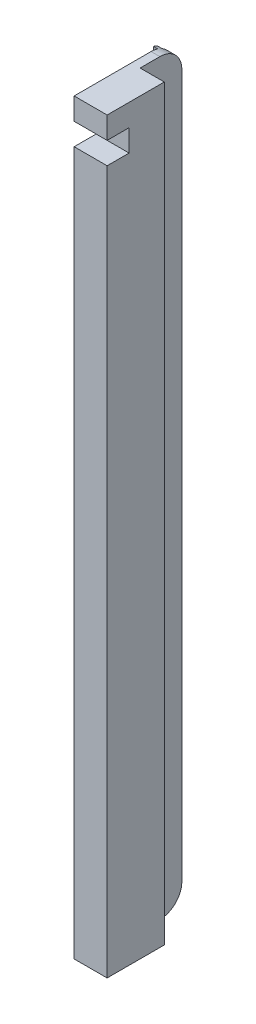
SolidWorks part; units mm, degrees
ref_plane "정면" through (0, 0, 0) normal (0, 0, 1) x (1, 0, 0)
ref_plane "윗면" through (0, 0, 0) normal (0, 1, 0) x (1, 0, 0)
ref_plane "우측면" through (0, 0, 0) normal (1, 0, 0) x (0, 0, -1)
sketch "스케치1" plane through (0, 0, 0) normal (0, 0, 1) x (1, 0, 0)
  line L0 (-318.5049, 0) -> (318.5049, 0) construction
  line L1 (0, 0) -> (0, -258.8265) construction
  line L2 (-168, 0) -> (168, 0)
  line L3 (-168, -20) -> (168, -20)
  line L4 (168, -20) -> (168, 0) construction
  line L5 (168, -20) -> (168, -340)
  line L6 (172, -340) -> (172, 0)
  line L7 (168, 0) -> (183, 0)
  line L8 (183, 0) -> (183, -340)
  line L9 (183, -340) -> (168, -340)
  line L10 (-168, -20) -> (-168, 0) construction
  line L11 (-183, -340) -> (-168, -340)
  line L12 (-183, 0) -> (-183, -340)
  line L13 (-168, 0) -> (-183, 0)
  line L14 (-172, -340) -> (-172, 0)
  line L15 (-168, -20) -> (-168, -340)
  line L16 (168, -20) -> (168, 0)
  line L17 (-168, -20) -> (-168, 0)
  point P14 (0, -20)
  dimension "D1" = 168
  dimension "D2" = 20
  dimension "D3" = 4
  dimension "D4" = 340
  dimension "D5" = 15
extrude "보스-돌출1" add sketch "스케치1" along normal blind 26 contours L3 L5 L9 L8 L7 L2 L13 L12 L11 L15
extrude "보스-돌출2" add sketch "스케치1<4>" against normal blind 19 contours L16 L5 L9 L6 L7 | L15 L17 L13 L14 L11 region at (-170, -170, 0) region at (170, -170, 0)
sketch "스케치1<4>" plane through (0, 0, 0) normal (0, 0, 1) x (1, 0, 0) same geometry as "스케치1"
fillet "필렛1" radius 10 4 edges at (-170, 0, -19) (170, 0, -19) (170, -340, -19) (-170, -340, -19)
sketch "스케치2" plane through (172, 0, 0) normal (1, 0, 0) x (0, 0, -1)
  line L0 (14, -340) -> (14, 0)
  line L1 (12, 0) -> (12, -340)
  line L4 (19, -330) -> (19, -10)
  line L5 (9, 0) -> (0, 0)
  line L6 (0, 0) -> (0, -340)
  line L7 (0, -340) -> (9, -340)
  line L8 (19, -330) -> (19, -10)
  line L9 (9, 0) -> (0, 0)
  line L10 (0, 0) -> (0, -340)
  line L11 (0, -340) -> (9, -340)
  arc A2 (19, -10) -> (9, 0) centre (9, -10) ccw
  arc A3 (9, -340) -> (19, -330) centre (9, -330) ccw
  arc A4 (19, -10) -> (9, 0) centre (9, -10) ccw
  arc A5 (9, -340) -> (19, -330) centre (9, -330) ccw
  dimension "D2" = 5
  dimension "D3" = 2
  dimension "D1" = 0
sketch "스케치3" plane through (168, 0, 0) normal (-1, 0, 0) x (0, 0, 1)
  line L0 (-12, 0) -> (-12, -340) construction
  line L1 (-14, -340) -> (-14, 0) construction
  line L2 (-12, 0) -> (-12, -340)
  line L3 (-14, -340) -> (-14, 0)
  line L4 (-19, -10) -> (-19, -330)
  line L5 (0, 0) -> (-9, 0)
  line L6 (0, -340) -> (0, 0)
  line L7 (-9, -340) -> (0, -340)
  line L8 (-19, -10) -> (-19, -330)
  line L9 (0, 0) -> (-9, 0)
  line L10 (0, -340) -> (0, 0)
  line L11 (-9, -340) -> (0, -340)
  arc A2 (-9, 0) -> (-19, -10) centre (-9, -10) ccw
  arc A3 (-19, -330) -> (-9, -340) centre (-9, -330) ccw
  arc A4 (-9, 0) -> (-19, -10) centre (-9, -10) ccw
  arc A5 (-19, -330) -> (-9, -340) centre (-9, -330) ccw
  arc M8 (-9, 0) -> (-19, -10) centre (-9, -10) ccw
  arc M10 (-19, -330) -> (-9, -340) centre (-9, -330) ccw
  dimension "D1" = 0
extrude "보스-돌출3" add sketch "스케치3" along normal blind 2 contours L3 L2 M10 M8 region at (168, -170, -12.9991)
mirror "대칭 복사1" about plane through (0, 0, 0) normal (1, 0, 0) of "보스-돌출3"
sketch "스케치5" plane through (0, 0, 0) normal (0, 1, 0) x (1, 0, 0)
  line L0 (-7, 0) -> (-7, -26)
  line L1 (7, 0) -> (7, -26)
  line L2 (-168, 0) -> (-168, -6)
  line L3 (-168, -6) -> (-7, -6)
  line L4 (7, -6) -> (168, -6)
  line L5 (168, -6) -> (168, 0)
  line L12 (-168, 0) -> (-168, 9)
  line L13 (-168, 9) -> (-172, 9)
  line L14 (-172, 9) -> (-172, 0)
  line L15 (-172, 0) -> (-183, 0)
  line L16 (-183, 0) -> (-183, -26)
  line L17 (-183, -26) -> (183, -26)
  line L18 (183, -26) -> (183, 0)
  line L19 (183, 0) -> (172, 0)
  line L20 (172, 0) -> (172, 9)
  line L21 (172, 9) -> (168, 9)
  line L22 (168, 9) -> (168, 0)
  line L23 (168, 0) -> (-168, 0)
  line L24 (-168, 0) -> (-168, 9)
  line L25 (-168, 9) -> (-172, 9)
  line L26 (-172, 9) -> (-172, 0)
  line L27 (-172, 0) -> (-183, 0)
  line L28 (-183, 0) -> (-183, -26)
  line L29 (-183, -26) -> (183, -26)
  line L30 (183, -26) -> (183, 0)
  line L31 (183, 0) -> (172, 0)
  line L32 (172, 0) -> (172, 9)
  line L33 (172, 9) -> (168, 9)
  line L34 (168, 9) -> (168, 0)
  line L35 (168, 0) -> (-168, 0)
  line M27 (168, 0) -> (-168, 0)
  dimension "D2" = 7
  dimension "D3" = 7
  dimension "D4" = 6
  dimension "D1" = 0
extrude "컷-돌출1" cut sketch "스케치5" against normal blind 52 contours L2 L3 L0 M27 | L4 L5 L1 M27 region at (-87.5, 0, 3) region at (87.5, 0, 3)
sketch "스케치6" plane through (168, 0, 0) normal (-1, 0, 0) x (0, 0, 1)
  line L0 (26, -20) -> (26, -340) construction
  line L1 (-71.7494, 105.886) -> (84.6976, 105.886)
  line L2 (-71.7494, 105.886) -> (-71.7494, -374.2228)
  line L3 (-71.7494, -374.2228) -> (84.6976, -374.2228)
  line L4 (84.6976, 105.886) -> (84.6976, -374.2228)
  line L5 (-71.7494, 105.886) -> (84.6976, -374.2228) construction
  line L6 (-71.7494, -374.2228) -> (84.6976, 105.886) construction
  line L7 (26, -340) -> (0, -340) construction
  line L8 (26, 0) -> (6, 0)
  line L9 (-9, 0) -> (6, 0)
  line L10 (-9, 0) -> (6, 0)
  line L11 (26, 0) -> (6, 0)
  line L12 (26, -20) -> (26, -340)
  line L13 (26, -20) -> (26, 0)
  line L14 (26, -20) -> (26, 0)
  line L15 (26, -20) -> (26, -340)
  line L16 (26, -20) -> (6, -20)
  line L17 (26, -20) -> (6, -20)
  line L18 (6, -20) -> (6, 0)
  line L19 (6, -20) -> (6, 0)
  point P0 (6.4741, -134.1684)
  line M5 (26, -20) -> (6, -20)
  line M6 (6, -20) -> (6, 0)
  line M7 (6, 0) -> (-9, 0)
  arc M8 (-9, 0) -> (-12, -0.4606) centre (-9, -10) ccw
  line M9 (-12, -0.4606) -> (-12, -339.5394)
  arc M10 (-12, -339.5394) -> (-9, -340) centre (-9, -330) ccw
  line M11 (-9, -340) -> (26, -340)
  line M12 (26, -340) -> (26, -20)
  dimension "D1" = 19.5259
  dimension "D2" = 240.0544
  dimension "D3" = 156.447
  dimension "D4" = 205.8316
extrude "컷-돌출3" cut sketch "스케치6" along normal blind 401 contours L4 L1 L2 L3 L14 L11 M12 M11 M10 M9 M8 M7 | L14 L11 M5 M6 | M12 M5 M6 M7 M8 M9 M10 M11 region at (168, 100.8364, 6.4741) region at (168, -10, 16) region at (168, -175.1122, 6.7138)
sketch "스케치7" plane through (168, 0, 0) normal (-1, 0, 0) x (0, 0, 1)
  line L0 (26, -20) -> (26, -340) construction
  line L1 (26, 0) -> (6, 0) construction
  line L2 (26, -20) -> (26, 0) construction
  line L3 (26, -20) -> (6, -20) construction
  line L4 (26, -340) -> (26, 0)
  line L5 (26, 0) -> (-9, 0)
  line L6 (-19, -10) -> (-19, -330)
  line L7 (-9, -340) -> (26, -340)
  line L8 (26, -340) -> (26, 0)
  line L9 (26, 0) -> (-9, 0)
  line L10 (-19, -10) -> (-19, -330)
  line L11 (-9, -340) -> (26, -340)
  line L12 (6, -20) -> (6, 0) construction
  line L13 (-9, 0) -> (6, 0) construction
  line L14 (-71.7494, 105.886) -> (84.6976, 105.886) construction
  line L15 (84.6976, 105.886) -> (84.6976, -374.2228) construction
  line L16 (-71.7494, -374.2228) -> (84.6976, -374.2228) construction
  line L17 (-71.7494, 105.886) -> (-71.7494, -374.2228) construction
  line L18 (26, -20) -> (26, -340)
  line L19 (26, 0) -> (6, 0)
  line L20 (26, -20) -> (26, 0)
  line L21 (26, -20) -> (6, -20)
  line L22 (6, -20) -> (6, 0)
  line L23 (-9, 0) -> (6, 0)
  line L24 (-71.7494, 105.886) -> (84.6976, 105.886)
  line L25 (84.6976, 105.886) -> (84.6976, -374.2228)
  line L26 (-71.7494, -374.2228) -> (84.6976, -374.2228)
  line L27 (-71.7494, 105.886) -> (-71.7494, -374.2228)
  line L29 (16, -10) -> (26, -10)
  line L30 (16, -10) -> (16, -20)
  line L31 (16, -20) -> (26, -20)
  line L32 (26, -10) -> (26, -20)
  line L33 (16, -10) -> (26, -20) construction
  line L34 (16, -20) -> (26, -10) construction
  arc A2 (-9, 0) -> (-19, -10) centre (-9, -10) ccw
  arc A3 (-19, -330) -> (-9, -340) centre (-9, -330) ccw
  arc A4 (-9, 0) -> (-19, -10) centre (-9, -10) ccw
  arc A5 (-19, -330) -> (-9, -340) centre (-9, -330) ccw
  point P15 (21, -15)
  dimension "D2" = 10
  dimension "D3" = 10
  dimension "D4" = 0
  dimension "D1" = 0
extrude "컷-돌출4" cut sketch "스케치7" against normal blind 401 contours L29 L30 L21 L8 region at (168, -15, 21)
extrude "보스-돌출5" add sketch "스케치3<3>" along normal blind 2 contours L3 L2 M10 M8 region at (168, -170, -12.9991)
sketch "스케치3<3>" plane through (168, 0, 0) normal (-1, 0, 0) x (0, 0, 1) same geometry as "스케치3"
